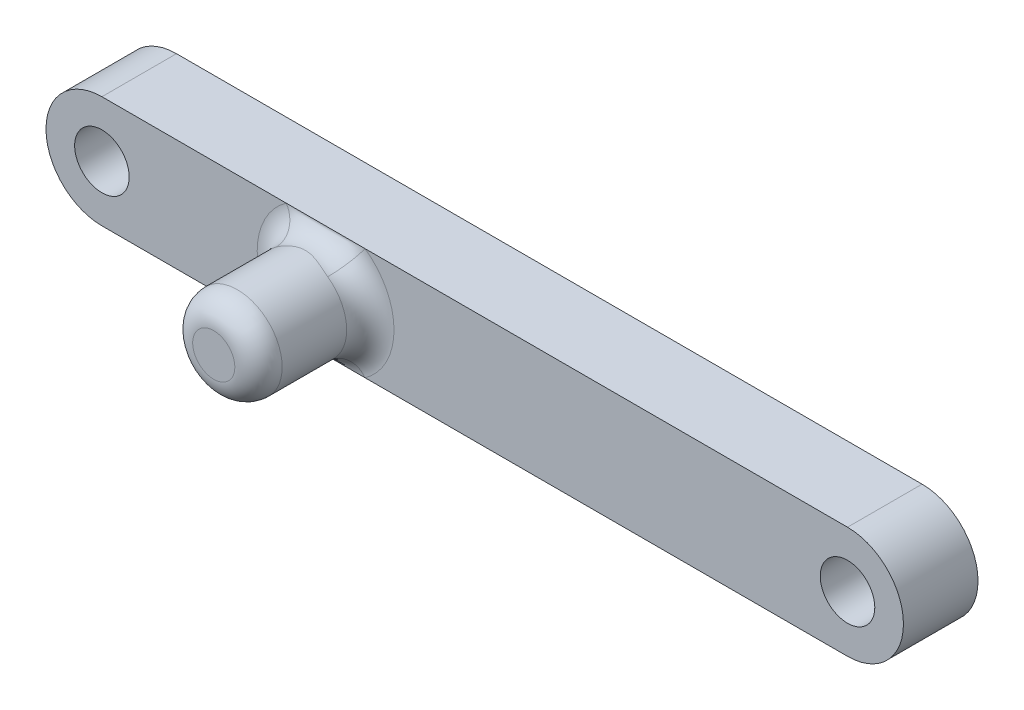
SolidWorks part; units mm, degrees
ref_plane "Front Plane" through (0, 0, 0) normal (0, 0, 1) x (1, 0, 0)
ref_plane "Top Plane" through (0, 0, 0) normal (0, 1, 0) x (1, 0, 0)
ref_plane "Right Plane" through (0, 0, 0) normal (1, 0, 0) x (0, 0, -1)
sketch "Sketch1" plane through (0, 0, 0) normal (0, 0, 1) x (1, 0, 0)
  line L0 (0, 0) -> (100, 0) construction
  line L1 (0, 7.5) -> (100, 7.5)
  line L2 (0, -7.5) -> (100, -7.5)
  arc A0 (0, 7.5) -> (0, -7.5) centre (0, 0) ccw
  arc A1 (100, -7.5) -> (100, 7.5) centre (100, 0) ccw
  circle A2 centre (0, 0) radius 3.6576
  circle A3 centre (100, 0) radius 3.6576
  point P3 (50, 0)
  dimension "D3" = 7.3152
  dimension "D1" = 100
  dimension "D2" = 15
extrude "Boss-Extrude1" add sketch "Sketch1" along normal blind 10
sketch "Sketch2" plane through (0, 0, 10) normal (0, 0, 1) x (1, 0, 0)
  line L0 (0, 0) -> (30, 0) construction
  circle A0 centre (30, 0) radius 6
  dimension "D2" = 12
  dimension "D1" = 30
extrude "Boss-Extrude2" add sketch "Sketch2" along normal blind 15
fillet "Fillet1" radius 3.175 2 edges at (36, 0, 25) (36, 0, 10)
